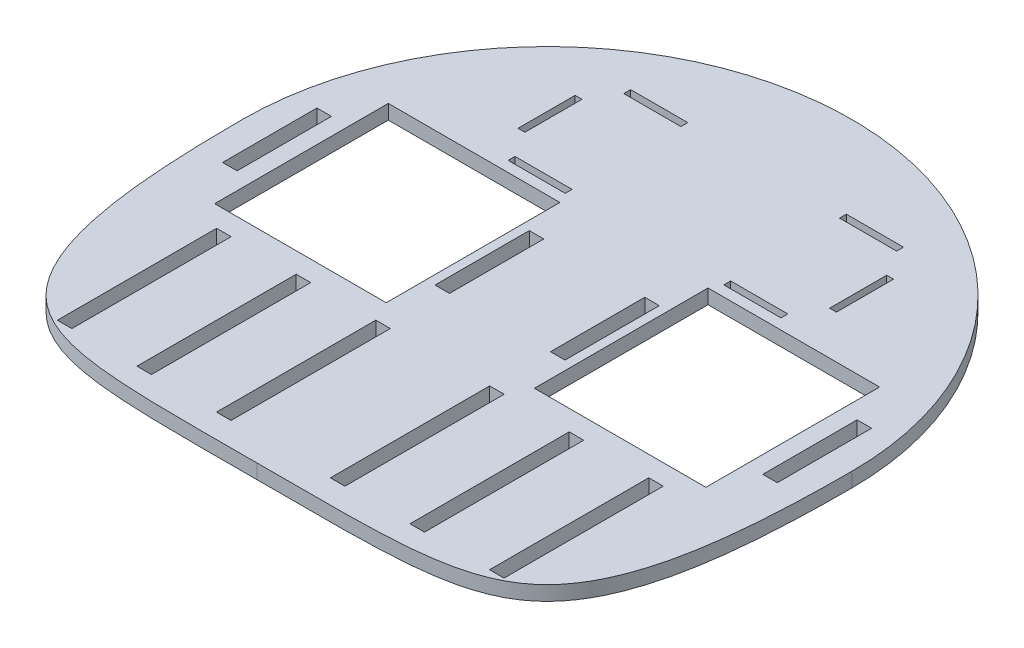
SolidWorks part; units mm, degrees
ref_plane "Front Plane" through (0, 0, 0) normal (0, 0, 1) x (1, 0, 0)
ref_plane "Top Plane" through (0, 0, 0) normal (0, 1, 0) x (1, 0, 0)
ref_plane "Right Plane" through (0, 0, 0) normal (1, 0, 0) x (0, 0, -1)
sketch "Sketch1" plane through (0, 0, 0) normal (0, 1, 0) x (1, 0, 0)
  line L0 (0, 0) -> (-157.9039, -157.9039) construction
  line L1 (0, -127) -> (0, 133.35) construction
  arc A0 (133.35, 0) -> (-133.35, 0) centre (0, 0) ccw
  spline S0 degree 3 poles (-133.35, 0) (-133.35, -51.198) (-123.8034, -129.8051) (-58.428, -127) (0, -127) knots 0 0 0 0 0.502616 1 1 1 1
  spline S1 degree 3 poles (133.35, 0) (133.35, -51.198) (123.8034, -129.8051) (58.428, -127) (0, -127) knots 0 0 0 0 0.502616 1 1 1 1
  dimension "D1" = 266.7
extrude "Base" add sketch "Sketch1" along normal blind 6.35
sketch "ShaftLayout" plane through (0, 6.35, 0) normal (0, 1, 0) x (1, 0, 0)
  line L0 (-133.35, 0) -> (133.35, 0) construction
  line L1 (0, 133.35) -> (0, -127) construction
  line L2 (-113.4353, -6.35) -> (-103.5293, -6.35)
  line L3 (-36.3853, -38) -> (-94.3853, -38)
  line L4 (-36.3853, -38) -> (-36.3853, 38)
  line L5 (-36.3853, 38) -> (-94.3853, 38)
  line L6 (-94.3853, -38) -> (-94.3853, 38)
  line L7 (-36.3853, -38) -> (-94.3853, 38) construction
  line L8 (-36.3853, 38) -> (-94.3853, -38) construction
  line L9 (-100.7353, -15.875) -> (-103.5293, -15.875)
  line L10 (-100.7353, -15.875) -> (-100.7353, 15.875)
  line L11 (-100.7353, 15.875) -> (-103.5293, 15.875)
  line L12 (-103.5293, -15.875) -> (-103.5293, 15.875)
  line L13 (-100.7353, -15.875) -> (-103.5293, 15.875) construction
  line L14 (-100.7353, 15.875) -> (-103.5293, -15.875) construction
  line L15 (-113.4353, -6.35) -> (-113.4353, 6.35)
  line L16 (-103.5293, -6.35) -> (-103.5293, 6.35)
  line L17 (-113.4353, 6.35) -> (-103.5293, 6.35)
  line L18 (-113.4353, -6.35) -> (-103.5293, 6.35) construction
  line L19 (-103.5293, -6.35) -> (-113.4353, 6.35) construction
  line L20 (-115.0228, -9.525) -> (-113.4353, -9.525)
  line L21 (-115.0228, -9.525) -> (-115.0228, 9.525)
  line L22 (-113.4353, -9.525) -> (-113.4353, 9.525)
  line L23 (-115.0228, 9.525) -> (-113.4353, 9.525)
  line L24 (-115.0228, -9.525) -> (-113.4353, 9.525) construction
  line L25 (-113.4353, -9.525) -> (-115.0228, 9.525) construction
  line L26 (-126.1353, -7.9375) -> (-115.0228, -7.9375)
  line L27 (-126.1353, -7.9375) -> (-126.1353, 7.9375)
  line L28 (-115.0228, -7.9375) -> (-115.0228, 7.9375)
  line L29 (-126.1353, 7.9375) -> (-115.0228, 7.9375)
  line L30 (-126.1353, -7.9375) -> (-115.0228, 7.9375) construction
  line L31 (-115.0228, -7.9375) -> (-126.1353, 7.9375) construction
  line L32 (-17.3353, -7.9375) -> (-28.4478, -7.9375)
  line L33 (-30.0353, -9.525) -> (-28.4478, -9.525)
  line L34 (-30.0353, -9.525) -> (-30.0353, 9.525)
  line L35 (-30.0353, 9.525) -> (-28.4478, 9.525)
  line L36 (-28.4478, -9.525) -> (-28.4478, 9.525)
  line L37 (-30.0353, -9.525) -> (-28.4478, 9.525) construction
  line L38 (-30.0353, 9.525) -> (-28.4478, -9.525) construction
  line L39 (-17.3353, -7.9375) -> (-17.3353, 7.9375)
  line L40 (-28.4478, -7.9375) -> (-28.4478, 7.9375)
  line L41 (-17.3353, 7.9375) -> (-28.4478, 7.9375)
  line L42 (-17.3353, -7.9375) -> (-28.4478, 7.9375) construction
  line L43 (-28.4478, -7.9375) -> (-17.3353, 7.9375) construction
  arc A0 (133.35, 0) -> (-133.35, 0) centre (0, 0) ccw construction
  point P10 (-65.3853, 0)
  point P15 (-102.1323, 0)
  point P20 (-29.2416, 0)
  point P21 (-108.4823, 0)
  point P22 (-114.2291, 0)
  point P23 (-120.5791, 0)
  point P41 (-22.8916, 0)
  dimension "D1" = 58
  dimension "D2" = 76
  dimension "D3" = 6.35
  dimension "D4" = 2.794
  dimension "D5" = 31.75
  dimension "D6" = 9.906
  dimension "D7" = 12.7
  dimension "D8" = 19.05
  dimension "D9" = 1.5875
  dimension "D10" = 12.7
  dimension "D11" = 15.875
  dimension "D12" = 19.05
  dimension "D13" = 1.5875
  dimension "D14" = 15.875
  dimension "D15" = 12.7
  dimension "D16" = 6.35
sketch "MotorLayout" plane through (0, 6.35, 0) normal (0, 1, 0) x (1, 0, 0)
  line L0 (-97.7353, -81.74) -> (-117.7353, -81.74) construction
  line L1 (-97.7353, -110.24) -> (-21.7353, -110.24)
  line L2 (-97.7353, -110.24) -> (-97.7353, -53.24)
  line L3 (-97.7353, -53.24) -> (-21.7353, -53.24)
  line L4 (-21.7353, -110.24) -> (-21.7353, -53.24)
  line L5 (-97.7353, -110.24) -> (-21.7353, -53.24) construction
  line L6 (-97.7353, -53.24) -> (-21.7353, -110.24) construction
  line L7 (-113.4353, -92.0587) -> (-103.5293, -92.0587)
  line L8 (-103.5293, -97.615) -> (-100.7353, -97.615)
  line L9 (-103.5293, -97.615) -> (-103.5293, -65.865)
  line L10 (-103.5293, -65.865) -> (-100.7353, -65.865)
  line L11 (-100.7353, -97.615) -> (-100.7353, -65.865)
  line L12 (-103.5293, -97.615) -> (-100.7353, -65.865) construction
  line L13 (-103.5293, -65.865) -> (-100.7353, -97.615) construction
  line L14 (-36.3853, -38) -> (-94.3853, -38) construction
  line L15 (-113.4353, -92.0587) -> (-113.4353, -71.4212)
  line L16 (-103.5293, -92.0587) -> (-103.5293, -71.4212)
  line L17 (-113.4353, -71.4212) -> (-103.5293, -71.4212)
  line L18 (-113.4353, -92.0587) -> (-103.5293, -71.4212) construction
  line L19 (-103.5293, -92.0587) -> (-113.4353, -71.4212) construction
  line L20 (-102.1323, -1000) -> (-102.1323, 49000) construction
  point P0 (-59.7353, -81.74)
  point P7 (-102.1323, -81.74)
  point P14 (-108.4823, -81.74)
  dimension "D1" = 20
  dimension "D2" = 76
  dimension "D3" = 57
  dimension "D4" = 2.794
  dimension "D5" = 15.24
  dimension "D6" = 31.75
  dimension "D7" = 20.6375
  dimension "D8" = 12.7
  dimension "D9" = 3
sketch "Sketch6" plane through (0, 6.35, 0) normal (0, 1, 0) x (1, 0, 0)
  line L0 (-36.3853, -38) -> (-36.3853, 38) construction
  line L1 (-32.4166, -38) -> (-107.4981, -38)
  line L2 (-32.4166, -38) -> (-32.4166, 38)
  line L3 (-32.4166, 38) -> (-107.4981, 38)
  line L4 (-107.4981, -38) -> (-107.4981, 38)
  line L5 (-28.4478, -9.525) -> (-28.4478, 9.525) construction
  line L6 (-103.5293, -15.875) -> (-103.5293, 15.875) construction
  line L7 (0, 133.35) -> (0, -127) construction
  line L8 (28.4478, 20.6375) -> (22.0978, -20.6375) construction
  line L9 (28.4478, -20.6375) -> (22.0978, 20.6375) construction
  line L10 (115.0228, 20.6375) -> (121.3728, -20.6375) construction
  line L11 (115.0228, -20.6375) -> (121.3728, 20.6375) construction
  line L12 (-133.35, 0) -> (133.35, 0) construction
  line L13 (-115.0228, -20.6375) -> (-121.3728, -20.6375)
  line L14 (-115.0228, -20.6375) -> (-115.0228, 20.6375)
  line L15 (-115.0228, 20.6375) -> (-121.3728, 20.6375)
  line L16 (-121.3728, -20.6375) -> (-121.3728, 20.6375)
  line L17 (-115.0228, -20.6375) -> (-121.3728, 20.6375) construction
  line L18 (-115.0228, 20.6375) -> (-121.3728, -20.6375) construction
  line L19 (-115.0228, -9.525) -> (-115.0228, 9.525) construction
  line L20 (-126.1353, 7.9375) -> (-115.0228, 7.9375) construction
  line L21 (-17.3353, 7.9375) -> (-28.4478, 7.9375) construction
  line L22 (-28.4478, -20.6375) -> (-22.0978, -20.6375)
  line L23 (-28.4478, -20.6375) -> (-28.4478, 20.6375)
  line L24 (-28.4478, 20.6375) -> (-22.0978, 20.6375)
  line L25 (-22.0978, -20.6375) -> (-22.0978, 20.6375)
  line L26 (-28.4478, -20.6375) -> (-22.0978, 20.6375) construction
  line L27 (-28.4478, 20.6375) -> (-22.0978, -20.6375) construction
  line L28 (22.0978, -20.6375) -> (22.0978, 20.6375)
  line L29 (28.4478, 20.6375) -> (22.0978, 20.6375)
  line L30 (28.4478, -20.6375) -> (28.4478, 20.6375)
  line L31 (28.4478, -20.6375) -> (22.0978, -20.6375)
  line L32 (121.3728, -20.6375) -> (121.3728, 20.6375)
  line L33 (115.0228, 20.6375) -> (121.3728, 20.6375)
  line L34 (115.0228, -20.6375) -> (115.0228, 20.6375)
  line L35 (115.0228, -20.6375) -> (121.3728, -20.6375)
  line L36 (107.4981, -38) -> (107.4981, 38)
  line L37 (32.4166, 38) -> (107.4981, 38)
  line L38 (32.4166, -38) -> (32.4166, 38)
  line L39 (32.4166, -38) -> (107.4981, -38)
  point P16 (-118.1978, 0)
  point P27 (-25.2728, 0)
  point P44 (25.2728, 0)
  point P45 (118.1978, 0)
  dimension "D1" = 3.9688
  dimension "D2" = 3.9688
  dimension "D3" = 12.7
  dimension "D4" = 12.7
  dimension "D5" = 6.35
  dimension "D6" = 6.35
extrude "WheelShaftCut" cut sketch "Sketch6" against normal through all
sketch "Sketch8" plane through (0, 6.35, 0) normal (0, 1, 0) x (1, 0, 0)
  line L0 (-97.7353, -81.74) -> (-21.7353, -81.74) construction
  line L1 (-21.7353, -110.24) -> (-21.7353, -53.24) construction
  line L2 (-97.7353, -53.24) -> (-21.7353, -53.24) construction
  line L3 (-21.7353, -116.59) -> (-28.0853, -116.59)
  line L4 (-21.7353, -116.59) -> (-21.7353, -46.89)
  line L5 (-21.7353, -46.89) -> (-28.0853, -46.89)
  line L6 (-28.0853, -116.59) -> (-28.0853, -46.89)
  line L7 (-21.7353, -116.59) -> (-28.0853, -46.89) construction
  line L8 (-21.7353, -46.89) -> (-28.0853, -116.59) construction
  line L9 (-56.5603, -116.59) -> (-62.9103, -116.59)
  line L10 (-56.5603, -116.59) -> (-56.5603, -46.89)
  line L11 (-56.5603, -46.89) -> (-62.9103, -46.89)
  line L12 (-62.9103, -116.59) -> (-62.9103, -46.89)
  line L13 (-56.5603, -116.59) -> (-62.9103, -46.89) construction
  line L14 (-56.5603, -46.89) -> (-62.9103, -116.59) construction
  line L15 (-91.3853, -116.59) -> (-97.7353, -116.59)
  line L16 (-91.3853, -116.59) -> (-91.3853, -46.89)
  line L17 (-91.3853, -46.89) -> (-97.7353, -46.89)
  line L18 (-97.7353, -116.59) -> (-97.7353, -46.89)
  line L19 (-91.3853, -116.59) -> (-97.7353, -46.89) construction
  line L20 (-91.3853, -46.89) -> (-97.7353, -116.59) construction
  line L21 (-97.7353, -110.24) -> (-97.7353, -53.24) construction
  line L22 (0, 133.35) -> (0, -127) construction
  line L23 (91.3853, -46.89) -> (97.7353, -116.59) construction
  line L24 (91.3853, -116.59) -> (97.7353, -46.89) construction
  line L25 (56.5603, -46.89) -> (62.9103, -116.59) construction
  line L26 (56.5603, -116.59) -> (62.9103, -46.89) construction
  line L27 (21.7353, -46.89) -> (28.0853, -116.59) construction
  line L28 (21.7353, -116.59) -> (28.0853, -46.89) construction
  line L29 (97.7353, -81.74) -> (21.7353, -81.74) construction
  line L30 (97.7353, -116.59) -> (97.7353, -46.89)
  line L31 (91.3853, -46.89) -> (97.7353, -46.89)
  line L32 (91.3853, -116.59) -> (91.3853, -46.89)
  line L33 (91.3853, -116.59) -> (97.7353, -116.59)
  line L34 (62.9103, -116.59) -> (62.9103, -46.89)
  line L35 (56.5603, -46.89) -> (62.9103, -46.89)
  line L36 (56.5603, -116.59) -> (56.5603, -46.89)
  line L37 (56.5603, -116.59) -> (62.9103, -116.59)
  line L38 (28.0853, -116.59) -> (28.0853, -46.89)
  line L39 (21.7353, -46.89) -> (28.0853, -46.89)
  line L40 (21.7353, -116.59) -> (21.7353, -46.89)
  line L41 (21.7353, -116.59) -> (28.0853, -116.59)
  point P5 (-24.9103, -81.74)
  point P14 (-59.7353, -81.74)
  point P19 (-94.5603, -81.74)
  point P42 (94.5603, -81.74)
  point P43 (59.7353, -81.74)
  point P44 (24.9103, -81.74)
  dimension "D1" = 6.35
  dimension "D2" = 6.35
  dimension "D3" = 3
extrude "Cut-Extrude3" cut sketch "Sketch8" against normal through all
sketch "BatteryLayout" plane through (0, 6.35, 0) normal (0, 1, 0) x (1, 0, 0)
  line L0 (0, 133.35) -> (0, -127) construction
  line L1 (-32.4166, 38) -> (-107.4981, 38) construction
  line L2 (-66.675, 45.62) -> (66.675, 45.62)
  line L3 (-66.675, 45.62) -> (-66.675, 93.245)
  line L4 (-66.675, 93.245) -> (66.675, 93.245)
  line L5 (66.675, 45.62) -> (66.675, 93.245)
  line L6 (-66.675, 45.62) -> (66.675, 93.245) construction
  line L7 (-66.675, 93.245) -> (66.675, 45.62) construction
  arc A0 (133.35, 0) -> (-133.35, 0) centre (0, 0) ccw construction
  point P6 (0, 69.4325)
  dimension "D1" = 133.35
  dimension "D2" = 47.625
  dimension "D3" = 7.62
sketch "Sketch10" plane through (0, 6.35, 0) normal (0, 1, 0) x (1, 0, 0)
  line L0 (-66.675, 93.245) -> (66.675, 93.245) construction
  line L1 (-59.69, 42.62) -> (-34.69, 42.62)
  line L2 (-59.69, 42.62) -> (-59.69, 45.62)
  line L3 (-59.69, 45.62) -> (-34.69, 45.62)
  line L4 (-34.69, 42.62) -> (-34.69, 45.62)
  line L5 (-59.69, 42.62) -> (-34.69, 45.62) construction
  line L6 (-59.69, 45.62) -> (-34.69, 42.62) construction
  line L7 (-59.69, 96.245) -> (-34.69, 96.245)
  line L8 (-59.69, 96.245) -> (-59.69, 93.245)
  line L9 (-59.69, 93.245) -> (-34.69, 93.245)
  line L10 (-34.69, 96.245) -> (-34.69, 93.245)
  line L11 (-59.69, 96.245) -> (-34.69, 93.245) construction
  line L12 (-59.69, 93.245) -> (-34.69, 96.245) construction
  line L13 (-66.675, 45.62) -> (66.675, 45.62) construction
  line L14 (-66.675, 45.62) -> (-66.675, 93.245) construction
  line L15 (0, 69.4325) -> (-66.675, 69.4325) construction
  line L16 (-66.675, 56.9325) -> (-69.675, 56.9325)
  line L17 (-66.675, 56.9325) -> (-66.675, 81.9325)
  line L18 (-66.675, 81.9325) -> (-69.675, 81.9325)
  line L19 (-69.675, 56.9325) -> (-69.675, 81.9325)
  line L20 (0, 133.35) -> (0, -127) construction
  line L21 (59.69, 93.245) -> (34.69, 96.245) construction
  line L22 (59.69, 96.245) -> (34.69, 93.245) construction
  line L23 (59.69, 45.62) -> (34.69, 42.62) construction
  line L24 (59.69, 42.62) -> (34.69, 45.62) construction
  line L25 (69.675, 56.9325) -> (69.675, 81.9325)
  line L26 (66.675, 81.9325) -> (69.675, 81.9325)
  line L27 (66.675, 56.9325) -> (66.675, 81.9325)
  line L28 (66.675, 56.9325) -> (69.675, 56.9325)
  line L29 (34.69, 96.245) -> (34.69, 93.245)
  line L30 (59.69, 93.245) -> (34.69, 93.245)
  line L31 (59.69, 96.245) -> (59.69, 93.245)
  line L32 (59.69, 96.245) -> (34.69, 96.245)
  line L33 (34.69, 42.62) -> (34.69, 45.62)
  line L34 (59.69, 45.62) -> (34.69, 45.62)
  line L35 (59.69, 42.62) -> (59.69, 45.62)
  line L36 (59.69, 42.62) -> (34.69, 42.62)
  point P0 (-47.19, 44.12)
  point P5 (-47.19, 94.745)
  point P20 (-66.675, 69.4325)
  point P40 (66.675, 69.4325)
  point P41 (47.19, 94.745)
  point P42 (47.19, 44.12)
  dimension "D1" = 3
  dimension "D2" = 3
  dimension "D3" = 25
  dimension "D4" = 25
  dimension "D5" = 6.985
  dimension "D6" = 6.985
  dimension "D7" = 3
  dimension "D8" = 25
extrude "Cut-Extrude4" cut sketch "Sketch10" against normal through all
